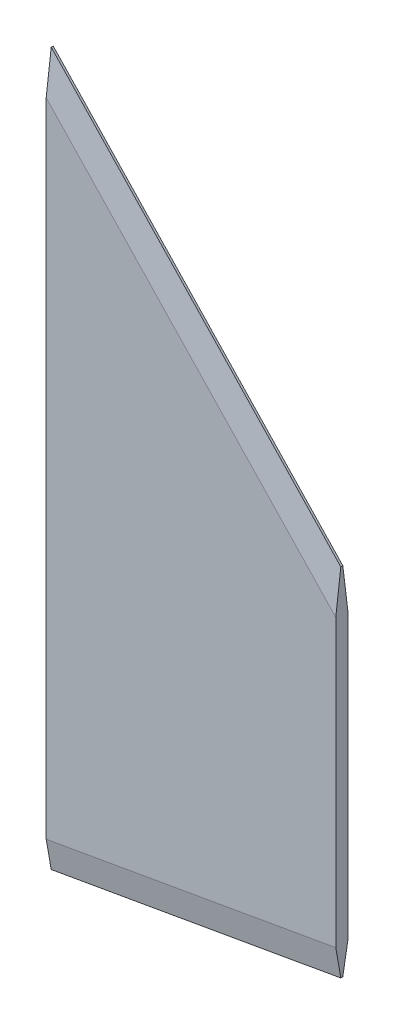
SolidWorks part; units mm, degrees
material "Hexcel AS4C (3000 Filaments)"
ref_plane "Front Plane" through (0, 0, 0) normal (0, 0, 1) x (1, 0, 0)
ref_plane "Top Plane" through (0, 0, 0) normal (0, 1, 0) x (1, 0, 0)
ref_plane "Right Plane" through (0, 0, 0) normal (1, 0, 0) x (0, 0, -1)
sketch "Sketch1" plane through (0, 0, 0) normal (0, 0, 1) x (1, 0, 0)
  line L0 (-60.9816, 52.6824) -> (-60.9816, -125.1176)
  line L1 (-60.9816, -125.1176) -> (11.3132, -112.4176)
  line L2 (11.3132, -112.4176) -> (11.3132, -23.5176)
  line L3 (11.3132, -23.5176) -> (-60.9816, 52.6824)
extrude "Boss-Extrude1" add sketch "Sketch1" along normal mid plane 3
chamfer "Chamfer1" distance 1.25 angle 80 4 edges at (-24.8342, -118.7676, -1.5) (-24.8342, -118.7676, 1.5) (-24.8342, 14.5824, -1.5) (-24.8342, 14.5824, 1.5) first distance on face at (-24.8342, -118.7676, 0) first distance on face at (-24.8342, 14.5824, 0)
